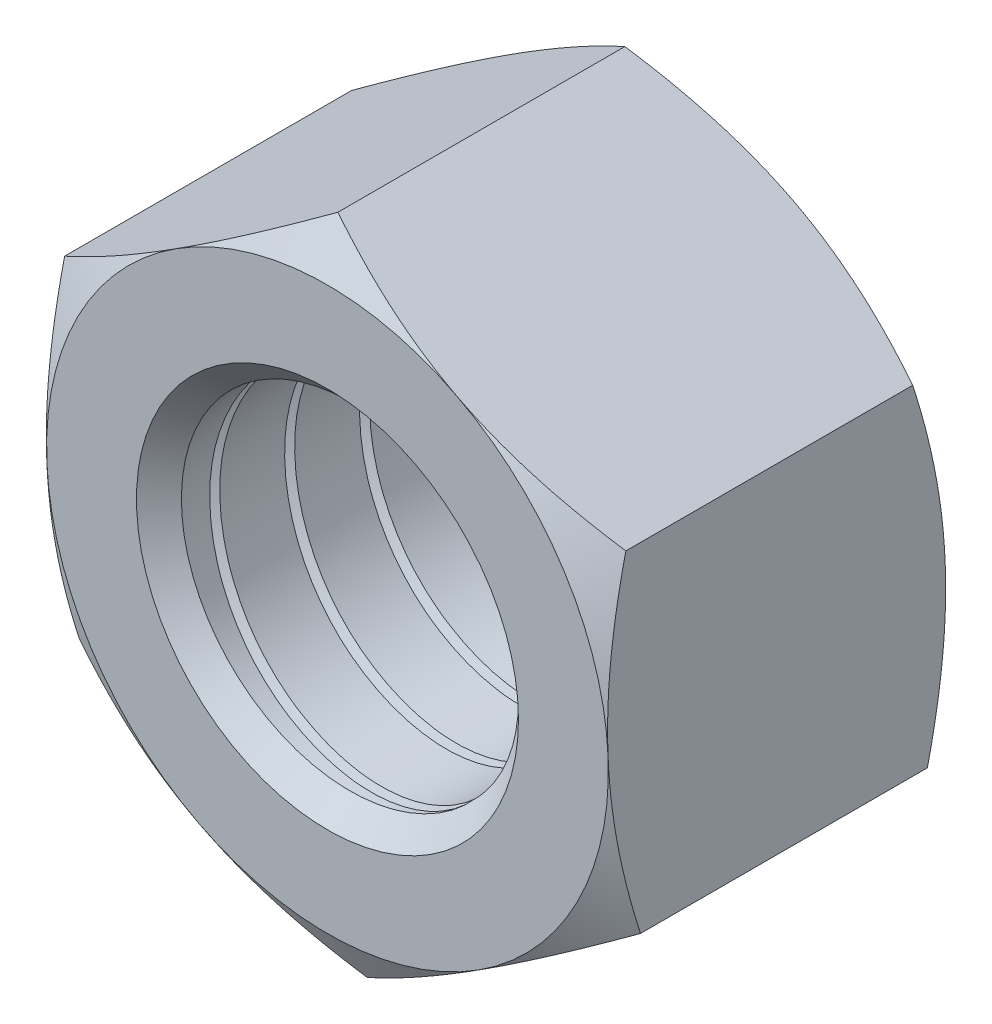
SolidWorks part; units mm, degrees
ref_plane "Front Plane" through (0, 0, 0) normal (0, 0, 1) x (1, 0, 0)
ref_plane "Top Plane" through (0, 0, 0) normal (0, 1, 0) x (1, 0, 0)
ref_plane "Right Plane" through (0, 0, 0) normal (1, 0, 0) x (0, 0, -1)
sketch "Sketch1" plane through (0, 0, 0) normal (0, 0, 1) x (1, 0, 0)
  line L1 (0.1302, -2.8838) -> (2.5626, -1.3292)
  line L2 (2.5626, -1.3292) -> (2.4324, 1.5547)
  line L3 (2.4324, 1.5547) -> (-0.1302, 2.8838)
  line L4 (-0.1302, 2.8838) -> (-2.5626, 1.3292)
  line L5 (-2.5626, 1.3292) -> (-2.4324, -1.5547)
  line L6 (-2.4324, -1.5547) -> (0.1302, -2.8838)
  circle A0 centre (0, 0) radius 2.5 construction
  dimension "D1" = 5
extrude "Boss-Extrude1" add sketch "Sketch1" along normal blind 1.5 and the other way blind 1.5
sketch "Sketch2" plane through (0, 0, -1.5) normal (0, 0, -1) x (-1, 0, 0)
  circle A0 centre (0, 0) radius 2.5
extrude "Cut-Extrude1" cut sketch "Sketch2" against normal blind 1.5 draft 60 flip side to cut
mirror "Mirror1" about plane through (0, 0, 0) normal (0, 0, 1) of "Cut-Extrude1"
sketch "Sketch3" plane through (0, 0, -1.5) normal (0, 0, -1) x (-1, 0, 0)
  circle A0 centre (0, 0) radius 1.5
extrude "Cut-Extrude2" cut sketch "Sketch3" against normal through all
chamfer "Chamfer1" distance 0.2 angle 45 2 edges at (-1.5, 0, -1.5) (-1.5, 0, 1.5)
sketch "Sketch5" plane through (0, 0, 1.5) normal (0, 0, 1) x (1, 0, 0)
  circle A0 centre (0, 0) radius 1.5
curve "Helix/Spiral1" pitch 0.6667 height 5 radius 1.5 centre (0, 0, 1.5) axis (0, 0, -1) start towards (1, 0, 0)
sketch "Sketch6" plane through (0, 0, 0) normal (0, 1, 0) x (1, 0, 0)
  line L1 (1.5774, -2) -> (0.7113, -1.5)
  line L2 (0.7113, -1.5) -> (0.7113, -2.5)
  line L3 (0.7113, -2.5) -> (1.5774, -2)
  circle A0 centre (1, -2) radius 0.2887 construction
  dimension "D1" = 1
sweep "Cut-Sweep1" cut profiles "Sketch6" path "Helix/Spiral1"
